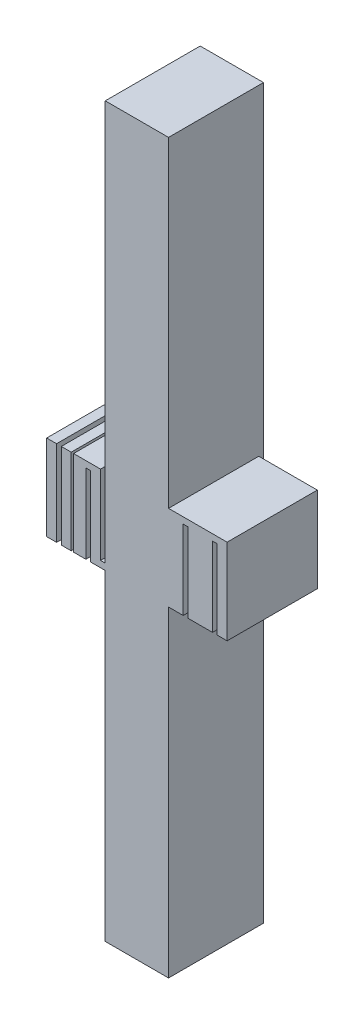
SolidWorks part; units mm, degrees
material "Air"
ref_plane "Front Plane" through (0, 0, 0) normal (0, 0, 1) x (1, 0, 0)
ref_plane "Top Plane" through (0, 0, 0) normal (0, 1, 0) x (1, 0, 0)
ref_plane "Right Plane" through (0, 0, 0) normal (1, 0, 0) x (0, 0, -1)
sketch "Sketch1" plane through (0, 0, 0) normal (0, 0, 1) x (1, 0, 0)
  line L1 (-10, -115) -> (10, -115)
  line L2 (-10, -115) -> (-10, 115)
  line L3 (-10, 115) -> (10, 115)
  line L4 (10, -115) -> (10, 115)
  line L5 (0, 115) -> (0, -115) construction
  line L6 (-10, 0) -> (10, 0) construction
  point P16 (0, 0)
extrude "Boss-Extrude1" add sketch "Sketch1" against normal blind 30
sketch "Sketch2" plane through (0, 0, 0) normal (0, 0, 1) x (1, 0, 0)
  line L0 (-10, 115) -> (-10, -115) construction
  line L1 (-28.5, -13.5) -> (-10, -13.5)
  line L2 (-28.5, -13.5) -> (-28.5, 13.5)
  line L3 (-28.5, 13.5) -> (-10, 13.5)
  line L4 (-10, -13.5) -> (-10, 13.5)
  line L5 (-19.25, 13.5) -> (-19.25, -13.5) construction
  line L6 (-28.5, 0) -> (-10, 0) construction
  line L7 (10, -115) -> (10, 115) construction
  line L8 (10, -13.5) -> (28.5, -13.5)
  line L9 (10, -13.5) -> (10, 13.5)
  line L10 (10, 13.5) -> (28.5, 13.5)
  line L11 (28.5, -13.5) -> (28.5, 13.5)
  line L12 (19.25, 13.5) -> (19.25, -13.5) construction
  line L13 (10, 0) -> (28.5, 0) construction
  point P20 (-19.25, 0)
  point P27 (19.25, 0)
extrude "Boss-Extrude2" add sketch "Sketch2" against normal blind 28.5
sketch "Sketch3" plane through (0, 0, 0) normal (0, 0, 1) x (1, 0, 0)
  line L1 (-11.5, -11.5) -> (-10, -11.5)
  line L2 (-11.5, -11.5) -> (-11.5, 13.5)
  line L3 (-11.5, 13.5) -> (-10, 13.5)
  line L4 (-10, -11.5) -> (-10, 13.5)
  line L5 (-10.75, 13.5) -> (-10.75, -11.5) construction
  line L6 (-11.5, 1) -> (-10, 1) construction
  point P20 (-10.75, 1)
extrude "Cut-Extrude1" cut sketch "Sketch3" against normal blind 28.5
sketch "Sketch4" plane through (0, 0, 0) normal (0, 0, 1) x (1, 0, 0)
  line L0 (-28.5, -13.5) -> (-10, -13.5) construction
  line L1 (-16.125, -13.5) -> (-14.625, -13.5)
  line L2 (-16.125, -13.5) -> (-16.125, 11.5)
  line L3 (-16.125, 11.5) -> (-14.625, 11.5)
  line L4 (-14.625, -13.5) -> (-14.625, 11.5)
  line L5 (-15.375, 11.5) -> (-15.375, -13.5) construction
  line L6 (-16.125, -1) -> (-14.625, -1) construction
  line L7 (-11.5, 13.5) -> (-28.5, 13.5) construction
  line L8 (-20.75, -13.5) -> (-20, -13.5)
  line L9 (-20.75, -13.5) -> (-20.75, 13.5)
  line L10 (-20.75, 13.5) -> (-20, 13.5)
  line L11 (-20, -13.5) -> (-20, 13.5)
  line L12 (-20.375, 13.5) -> (-20.375, -13.5) construction
  line L13 (-20.75, 0) -> (-20, 0) construction
  line L14 (10, -13.5) -> (28.5, -13.5) construction
  line L15 (-25.375, -13.5) -> (-23.875, -13.5)
  line L16 (-25.375, -13.5) -> (-25.375, 13.5)
  line L17 (-25.375, 13.5) -> (-23.875, 13.5)
  line L18 (-23.875, -13.5) -> (-23.875, 13.5)
  line L19 (-24.625, 13.5) -> (-24.625, -13.5) construction
  line L20 (-25.375, 0) -> (-23.875, 0) construction
  line L21 (14.625, -13.5) -> (16.125, -13.5)
  line L22 (14.625, -13.5) -> (14.625, 11.5)
  line L23 (14.625, 11.5) -> (16.125, 11.5)
  line L24 (16.125, -13.5) -> (16.125, 11.5)
  line L25 (15.375, 11.5) -> (15.375, -13.5) construction
  line L26 (14.625, -1) -> (16.125, -1) construction
  line L28 (23.875, -13.5) -> (25.375, -13.5)
  line L29 (23.875, -13.5) -> (23.875, 11.5)
  line L30 (23.875, 11.5) -> (25.375, 11.5)
  line L31 (25.375, -13.5) -> (25.375, 11.5)
  line L32 (24.625, 11.5) -> (24.625, -13.5) construction
  line L33 (23.875, -1) -> (25.375, -1) construction
  point P16 (-15.375, -1)
  point P31 (-20.375, 0)
  point P38 (-24.625, 0)
  point P47 (15.375, -1)
  point P58 (24.625, -1)
extrude "Cut-Extrude2" cut sketch "Sketch4" against normal blind 28.5
